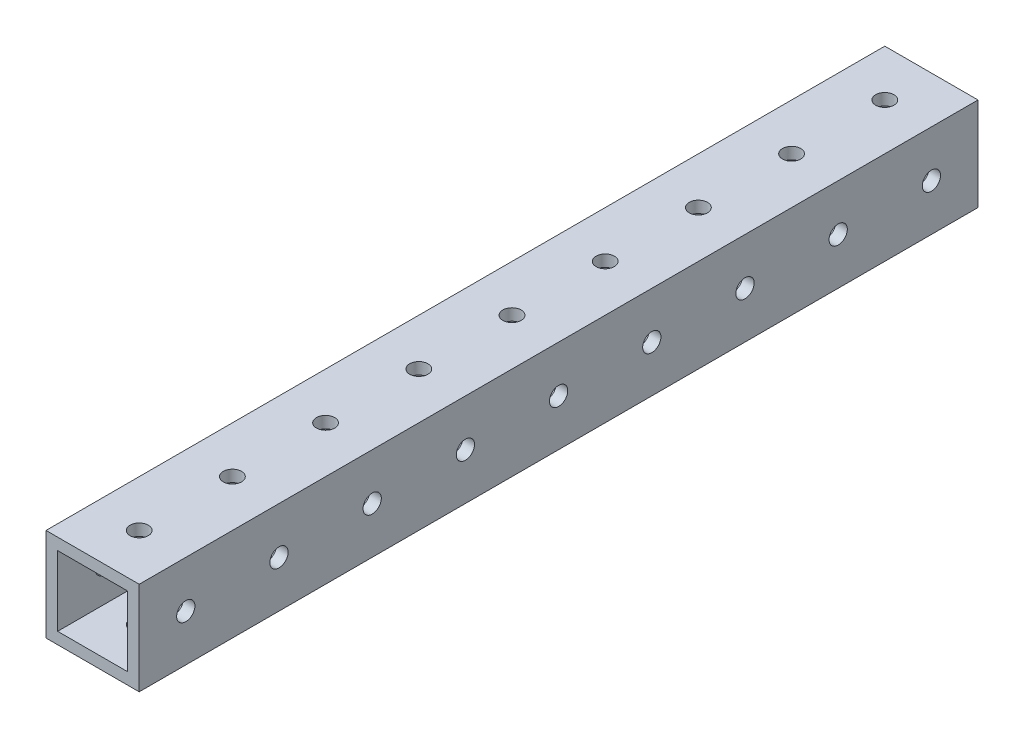
SolidWorks part; units mm, degrees
material "6061-T6 (SS)"
ref_plane "Front Plane" through (0, 0, 0) normal (0, 0, 1) x (1, 0, 0)
ref_plane "Top Plane" through (0, 0, 0) normal (0, 1, 0) x (1, 0, 0)
ref_plane "Right Plane" through (0, 0, 0) normal (1, 0, 0) x (0, 0, -1)
sketch "Sketch1" plane through (0, 0, 0) normal (0, 0, 1) x (1, 0, 0)
  line L1 (-12.7, -12.7) -> (12.7, -12.7)
  line L2 (-12.7, -12.7) -> (-12.7, 12.7)
  line L3 (-12.7, 12.7) -> (12.7, 12.7)
  line L4 (12.7, -12.7) -> (12.7, 12.7)
  line L5 (-12.7, -12.7) -> (12.7, 12.7) construction
  line L6 (-12.7, 12.7) -> (12.7, -12.7) construction
  point P0 (0, 0)
  dimension "D1" = 25.4
  dimension "D2" = 25.4
extrude "Boss-Extrude1" add sketch "Sketch1" along normal mid plane 228.6
shell "Shell1" thickness 3.175 removed face at (0, 0, -114.3) removed face at (0, 0, 114.3)
sketch "Sketch2" plane through (0, 12.7, 0) normal (0, 1, 0) x (1, 0, 0)
  line L0 (12.7, -114.3) -> (-12.7, -114.3) construction
  line L1 (12.7, -114.3) -> (12.7, 114.3) construction
  circle A0 centre (0, -101.6) radius 2.4892
  circle A1 centre (0, -76.2) radius 2.4892
  circle A2 centre (0, -50.8) radius 2.4892
  circle A3 centre (0, -25.4) radius 2.4892
  circle A4 centre (0, 0) radius 2.4892
  circle A5 centre (0, 25.4) radius 2.4892
  circle A6 centre (0, 50.8) radius 2.4892
  circle A7 centre (0, 76.2) radius 2.4892
  circle A8 centre (0, 101.6) radius 2.4892
  circle A9 centre (0, 127) radius 2.4892
  dimension "D1" = 4.9784
  dimension "D2" = 12.7
  dimension "D3" = 12.7
  dimension "D4" = 10
extrude "Cut-Extrude1" cut sketch "Sketch2" against normal through all
sketch "Sketch3" plane through (-12.7, 0, 0) normal (-1, 0, 0) x (0, 0, 1)
  line L0 (114.3, -12.7) -> (-114.3, -12.7) construction
  line L1 (114.3, 12.7) -> (114.3, -12.7) construction
  circle A0 centre (101.6, 0) radius 2.4892
  circle A1 centre (76.2, 0) radius 2.4892
  circle A2 centre (50.8, 0) radius 2.4892
  circle A3 centre (25.4, 0) radius 2.4892
  circle A4 centre (0, 0) radius 2.4892
  circle A5 centre (-25.4, 0) radius 2.4892
  circle A6 centre (-50.8, 0) radius 2.4892
  circle A7 centre (-76.2, 0) radius 2.4892
  circle A8 centre (-101.6, 0) radius 2.4892
  circle A9 centre (-127, 0) radius 2.4892
  dimension "D3" = 4.9784
  dimension "D1" = 12.7
  dimension "D2" = 12.7
  dimension "D4" = 10
extrude "Cut-Extrude2" cut sketch "Sketch3" against normal through all
